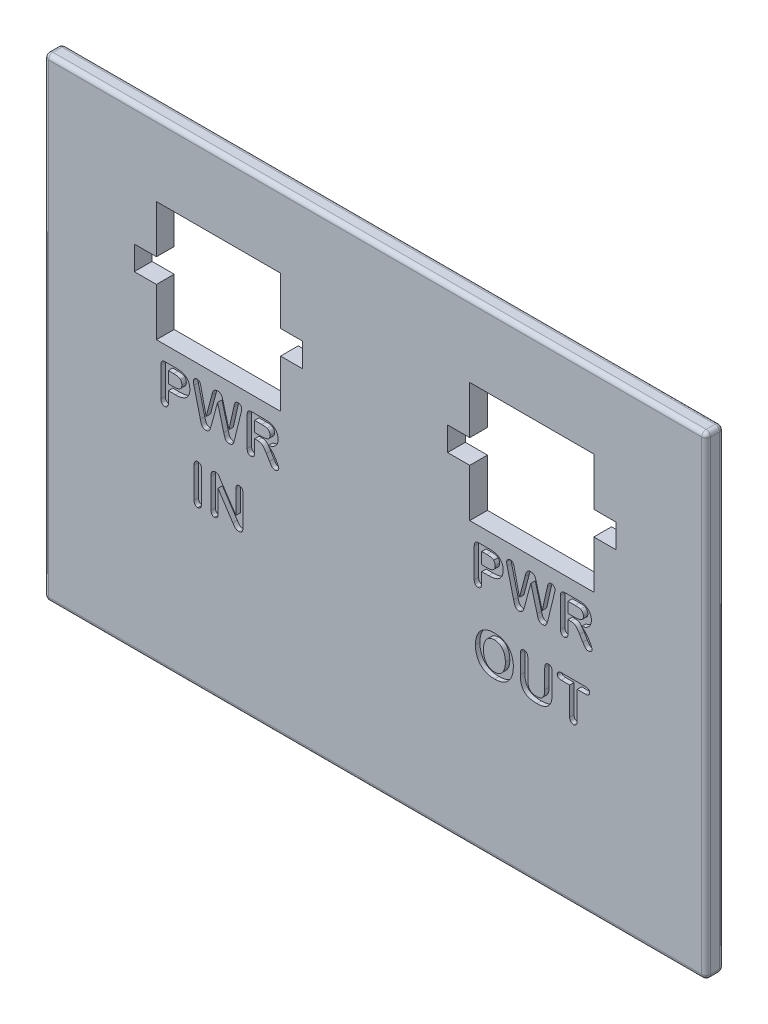
SolidWorks part; units mm, degrees
ref_plane "Front Plane" through (0, 0, 0) normal (0, 0, 1) x (1, 0, 0)
ref_plane "Top Plane" through (0, 0, 0) normal (0, 1, 0) x (1, 0, 0)
ref_plane "Right Plane" through (0, 0, 0) normal (1, 0, 0) x (0, 0, -1)
sketch "Sketch1" plane through (0, 0, 0) normal (0, 0, 1) x (1, 0, 0)
  line L1 (-37.35, -26.75) -> (37.35, -26.75)
  line L2 (-37.35, -26.75) -> (-37.35, 26.75)
  line L3 (-37.35, 26.75) -> (37.35, 26.75)
  line L4 (37.35, -26.75) -> (37.35, 26.75)
  line L5 (-37.35, -26.75) -> (37.35, 26.75) construction
  line L6 (-37.35, 26.75) -> (37.35, -26.75) construction
  point P0 (0, 0)
  dimension "D1" = 74.7
  dimension "D2" = 53.5
extrude "Boss-Extrude1" add sketch "Sketch1" along normal blind 2
sketch "Sketch5" plane through (0, 0, 2) normal (0, 0, 1) x (1, 0, 0)
  line L0 (-37.35, 26.75) -> (-37.35, -26.75) construction
  line L5 (37.35, 26.75) -> (-37.35, 26.75) construction
  line L6 (-37.35, -26.75) -> (37.35, -26.75) construction
  line L11 (10.675, 18.5) -> (10.675, 13.1)
  line L12 (10.675, 13.1) -> (8.175, 13.1)
  line L22 (-35.35, 26.75) -> (-35.35, -24.75) construction
  line L23 (-35.35, -24.75) -> (35.35, -24.75) construction
  line L24 (35.35, 26.75) -> (35.35, -24.75) construction
  line L25 (8.175, 13.1) -> (8.175, 10.4)
  line L26 (37.35, -26.75) -> (37.35, 26.75) construction
  line L27 (0, 0) -> (0, 5) construction
  line L37 (8.175, 10.4) -> (10.675, 10.4)
  line L38 (10.675, 10.4) -> (10.675, 5)
  line L39 (10.675, 5) -> (24.675, 5)
  line L40 (24.675, 5) -> (24.675, 10.4)
  line L41 (24.675, 10.4) -> (27.175, 10.4)
  line L42 (27.175, 10.4) -> (27.175, 13.1)
  line L43 (27.175, 13.1) -> (24.675, 13.1)
  line L44 (24.675, 13.1) -> (24.675, 18.5)
  line L45 (24.675, 18.5) -> (10.675, 18.5)
  line L46 (10.675, 13.1) -> (24.675, 13.1) construction
  line L47 (24.675, 10.4) -> (10.675, 10.4) construction
  line L48 (10.675, 10.4) -> (10.675, 13.1) construction
  line L49 (24.675, 13.1) -> (24.675, 10.4) construction
  line L50 (-10.675, 5) -> (0, 5) construction
  line L51 (0, 5) -> (10.675, 5) construction
  line L52 (-24.675, 18.5) -> (-24.675, 13.1)
  line L53 (-24.675, 13.1) -> (-27.175, 13.1)
  line L54 (-27.175, 13.1) -> (-27.175, 10.4)
  line L55 (-27.175, 10.4) -> (-24.675, 10.4)
  line L56 (-24.675, 10.4) -> (-24.675, 5)
  line L57 (-24.675, 5) -> (-10.675, 5)
  line L58 (-10.675, 5) -> (-10.675, 10.4)
  line L59 (-10.675, 10.4) -> (-8.175, 10.4)
  line L60 (-8.175, 10.4) -> (-8.175, 13.1)
  line L61 (-8.175, 13.1) -> (-10.675, 13.1)
  line L62 (-10.675, 13.1) -> (-10.675, 18.5)
  line L63 (-10.675, 18.5) -> (-24.675, 18.5)
  line L64 (-24.675, 13.1) -> (-10.675, 13.1) construction
  line L65 (-10.675, 10.4) -> (-24.675, 10.4) construction
  line L66 (-24.675, 10.4) -> (-24.675, 13.1) construction
  line L67 (-10.675, 13.1) -> (-10.675, 10.4) construction
  line L68 (-24.675, 5) -> (-35.35, 5) construction
  line L69 (24.675, 5) -> (35.35, 5) construction
  dimension "D7" = 14
  dimension "D3" = 2
  dimension "D4" = 14
  dimension "D5" = 13.5
  dimension "D6" = 2.7
  dimension "D8" = 2.5
  dimension "D9" = 5.4
  dimension "D10" = 2
  dimension "D11" = 13.5
  dimension "D12" = 2
  dimension "D13" = 19
  dimension "D14" = 2.7
  dimension "D15" = 5
  dimension "D20" = 2.5
  dimension "D21" = 5.4
  dimension "D22" = 19
extrude "Cut-Extrude1" cut sketch "Sketch5" against normal through all contours L62 L63 L52 L53 L54 L55 L56 L57 L58 L59 L60 L61 | L25 L37 L38 L39 L40 L41 L42 L43 L44 L45 L11 L12 region at (-17.675, 11.75, 2)
fillet "Fillet1" radius 0.5 12 edges at (0, -26.75, 2) (0, -26.75, 0) (-37.35, 0, 2) (-37.35, -26.75, 1) (-37.35, 0, 0) (0, 26.75, 2) (-37.35, 26.75, 1) (0, 26.75, 0) (37.35, -26.75, 1) (37.35, 0, 2) (37.35, 26.75, 1) (37.35, 0, 0)
sketch "Sketch6" plane through (0, 0, 2) normal (0, 0, 1) x (1, 0, 0)
  line L0 (-24.675, -1) -> (-10.675, -1) construction
  line L5 (-24.675, -1) -> (-24.675, 5) construction
  line L7 (-24.675, 5) -> (-10.675, 5) construction
  line L8 (10.675, -1) -> (24.675, -1) construction
  line L9 (10.675, -1) -> (10.675, 5) construction
  line L10 (10.675, 5) -> (24.675, 5) construction
  line L11 (24.675, -1) -> (24.675, 5) construction
  line L15 (-10.675, -1) -> (-10.675, 5) construction
  text T0 "PWR\r\nIN" font "Arial Rounded MT Bold" height 4.5
  text T1 "PWR\r\nOUT" font "Arial Rounded MT Bold" height 4.5
  dimension "D1" = 6
  dimension "D2" = 6
extrude "Cut-Extrude2" cut sketch "Sketch6" against normal blind 0.5
